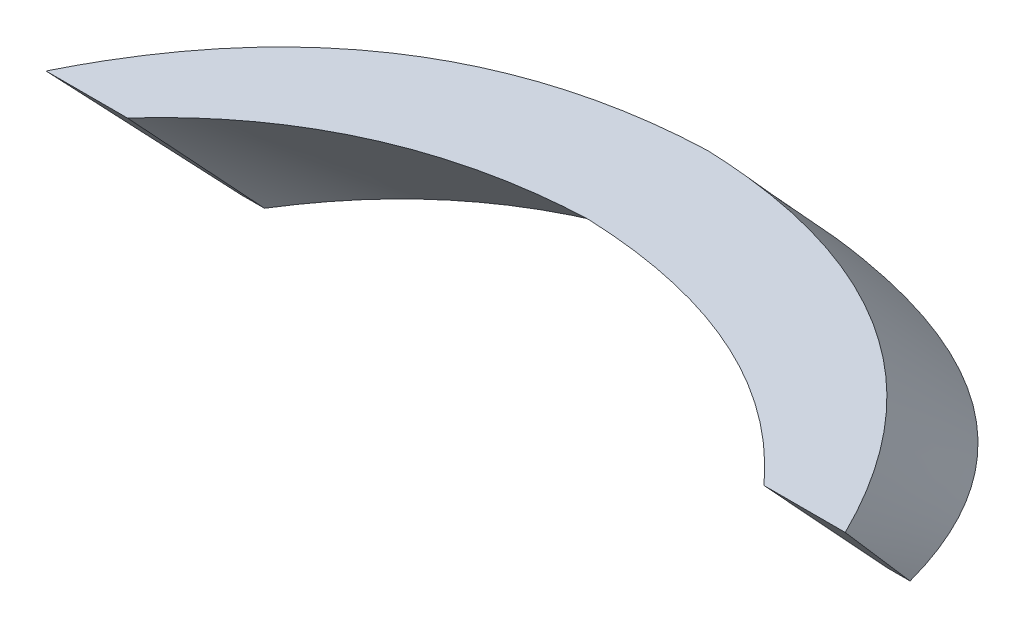
SolidWorks part; units mm, degrees
ref_plane "Front Plane" through (0, 0, 0) normal (0, 0, 1) x (1, 0, 0)
ref_plane "Top Plane" through (0, 0, 0) normal (0, 1, 0) x (1, 0, 0)
ref_plane "Right Plane" through (0, 0, 0) normal (1, 0, 0) x (0, 0, -1)
sketch "Sketch2" plane through (0, 0, 0) normal (0, 1, 0) x (1, 0, 0)
  line L0 (0, -5194.446) -> (0, 1731.482)
  line L1 (0, 0) -> (-18096.1342, 0) construction
  line L2 (0, 0) -> (-22098, -13277.818) construction
  line L3 (-22098, -15095.8741) -> (-22098, -12671.7993)
  line L4 (-22098, -12671.7993) -> (0, 1731.482)
  line L5 (-22098, -15095.8741) -> (0, -5194.446)
  line L6 (-9275.7037, -4314.3398) -> (-9275.7037, -5573.4051) construction
  line L7 (-9275.7037, -5573.4051) -> (-9275.7037, -9350.601) construction
  line L8 (-9275.7037, -5573.4051) -> (0, -5573.4051) construction
  line L9 (0, 346.2964) -> (-6827.52, -3825.6374)
  line L10 (0, -29565.6) -> (-7316.724, -34881.5112) construction
  line L11 (0, -29565.6) -> (-8167.6786, -29565.6) construction
  line L12 (0, -28507.0982) -> (0, -32741.1055)
  line L13 (-7316.724, -35992.9378) -> (-7316.724, -34511.0356)
  line L14 (-7316.724, -34511.0356) -> (0, -28507.0982)
  line L15 (0, -32741.1055) -> (-7316.724, -35992.9378)
  line L16 (-2399.2704, -30475.8849) -> (-2399.2704, -31308.772) construction
  line L17 (-2399.2704, -31308.772) -> (-2399.2704, -33807.4331) construction
  line L18 (-2399.2704, -31308.772) -> (0, -31308.772) construction
  line L19 (-6827.52, -3825.6374) -> (-6827.52, -6593.1427)
  line L20 (-6827.52, -6593.1427) -> (0, -3116.6676)
  line L21 (0, 346.2964) -> (0, -3116.6676) construction
  line L22 (0, -3116.6676) -> (0, 346.2964) construction
  line L23 (0, 346.2964) -> (0, -1385.1856) construction
  line L24 (0, 346.2964) -> (0, -3116.6676) construction
  line L25 (0, -1385.1856) -> (-6827.52, -5209.39) construction
  line L26 (0, 346.2964) -> (-22098, -13156.6142) construction
  line L27 (-3160.776, -1585.0854) -> (-3160.776, -3155.5874) construction
  line L28 (-3160.776, -3155.5874) -> (-3160.776, -4726.0893) construction
  line L29 (-3160.776, -3155.5874) -> (0, -3155.5874) construction
  dimension "Wing Sweep" = 31
  dimension "Half Span" = 22098
  dimension "Wing Root" = 6925.928
  dimension "D4" = 1731.482
  dimension "Wing Tip" = 2424.0748
  dimension "D6" = 606.0187
  dimension "Wing YBar" = 9275.7037
  dimension "Tail Sweep" = 36
  dimension "Tail Root" = 4234.0073
  dimension "D10" = 1058.5018
  dimension "Tail Tip" = 1481.9022
  dimension "D12" = 370.4756
  dimension "D13" = 7316.724
  dimension "Tail Ybar" = 2399.2704
  dimension "First Spar" = 1385.1856
  dimension "Second Spar" = 4848.1496
  dimension "Fuel Tip" = 2767.5053
  dimension "Tip Spar" = 484.815
  dimension "Fuel Ybar" = 3160.776
  dimension "Fuel Tank Length" = 6827.52
  dimension "Tail Arm" = 29565.6
sketch "Sketch4" plane through (0, 0, 0) normal (0, 1, 0) x (1, 0, 0)
  line L0 (0, 18200.9949) -> (0, -34834.2051) construction
  line L1 (-2240.28, 18200.9949) -> (2240.28, 18200.9949) construction
  line L2 (-2240.28, 11480.1549) -> (-2240.28, -25873.0851)
  line L3 (-2240.28, -34834.2051) -> (2240.28, -34834.2051) construction
  line L4 (2240.28, 11480.1549) -> (2240.28, -25873.0851)
  line L5 (0, -5194.446) -> (0, 1731.482) construction
  line L6 (-9275.7037, -5573.4051) -> (0, -5573.4051) construction
  line L7 (-2399.2704, -31308.772) -> (0, -31308.772) construction
  line L8 (0, 0) -> (-22098, -13277.818) construction
  line L9 (-22098, -12671.7993) -> (0, 1731.482) construction
  line L10 (-8451.85, 1616.4392) -> (-6132.83, 1616.4392)
  line L11 (-8451.85, 1616.4392) -> (-8451.85, -3941.0808)
  line L12 (-8451.85, -3941.0808) -> (-6132.83, -3941.0808)
  line L13 (-6132.83, 1616.4392) -> (-6132.83, -3941.0808)
  line L14 (2240.28, 11480.1549) -> (-2240.28, 11480.1549)
  arc A0 (-2240.28, -25873.0851) -> (2240.28, -25873.0851) centre (0, -25873.0851) ccw construction
  spline S0 degree 2 poles (-2240.28, 11480.1549) (-2010.8321, 15064.3252) (0, 18200.9949) knots 0 0 0 1 1 1 construction
  spline S1 degree 2 poles (2240.28, 11480.1549) (2010.8321, 15064.3252) (0, 18200.9949) knots 0 0 0 1 1 1 construction
  spline S2 degree 3 poles (-2240.28, -25873.0851) (-2042.135, -27711.7659) (-2075.1921, -30173.7144) (-919.8513, -32825.3563) (0, -32741.1055) knots 0 0 0 0 0.711043 1 1 1 1 construction
  spline S3 degree 3 poles (2240.28, -25873.0851) (2042.135, -27711.7659) (2075.1921, -30173.7144) (919.8513, -32825.3563) (0, -32741.1055) knots 0 0 0 0 0.711043 1 1 1 1 construction
  spline S4 degree 2 poles (-2240.28, -25873.0851) (-1878.6262, -27707.4335) (0, -28507.0982) knots 0 0 0 1 1 1
  spline S5 degree 2 poles (2240.28, -25873.0851) (1878.6262, -27707.4335) (0, -28507.0982) knots 0 0 0 1 1 1
  point P6 (0, 11480.1549)
  point P7 (0, -25873.0851)
  point P8 (0, -5573.4051)
  point P15 (0, -28113.3651)
  point P28 (-7292.34, 1616.4392)
  point P29 (-7292.34, -3021.6008)
  point P35 (-7292.34, -4381.6799)
  point P44 (-7292.34, -606.5688)
  dimension "Fuse Length" = 53035.2
  dimension "Fuse Dia" = 4480.56
  dimension "D3" = 6720.84
  dimension "D4" = 8961.12
  dimension "D6" = 7292.34
  dimension "Engine Dia" = 2319.02
  dimension "Engine Length" = 5557.52
  dimension "D9" = 4638.04
  dimension "D10" = 2223.008
  dimension "D11" = 4966.8362
  dimension "D2" = 23774.4
extrude "Boss-Extrude1" add sketch "Sketch4" along normal blind 76.2 contours L14 L2 S4 S5 L4
sketch "Sketch6" plane through (0, 0, 0) normal (0, 0, 1) x (1, 0, 0)
  line L0 (2240.28, 609.6) -> (-2240.28, 609.6) construction
  line L4 (-2240.28, 76.2) -> (-2240.28, 0) construction
  line L5 (2240.28, 76.2) -> (2240.28, 0) construction
  circle A2 centre (0, 609.6) radius 2240.28
  circle A3 centre (0, 609.6) radius 2151.38
  dimension "D2" = 88.9
  dimension "D1" = 4480.56
  dimension "D3" = 609.6
extrude "Boss-Extrude2" add sketch "Sketch6" along normal up to vertex (25873.0851 mm away) and the other way up to vertex (11480.1549 mm away) up to point (0, 0, 25873.0851) other way up to point (0, 0, -11480.1549)
sketch "Sketch38" plane through (0, 0, -11480.1549) normal (0, 0, -1) x (-1, 0, 0)
  arc A0 (-2155.7463, 0) -> (2155.7463, 0) centre (0, 609.6) ccw construction
  point P0 (0, -1630.68)
ref_plane "Plane1" through (0, 609.6, 0) normal (0, 1, 0) x (1, 0, 0)
sketch "Sketch9" plane through (0, 0, -11480.1549) normal (0, 0, -1) x (-1, 0, 0)
  circle A0 centre (0, 609.6) radius 2240.28
  arc A1 (2084.2074, 76.2) -> (-2084.2074, 76.2) centre (0, 609.6) ccw construction
  arc A2 (2175.8536, 76.2) -> (-2175.8536, 76.2) centre (0, 609.6) ccw construction
  circle A3 centre (0, 609.6) radius 2603.8351
extrude "Cut-Extrude2" cut sketch "Sketch9" against normal through all both and the other way through all
sketch "Sketch10" plane through (0, 0, 0) normal (0, 1, 0) x (1, 0, 0)
  line L0 (-22098, -12671.7993) -> (-2240.28, 271.2873)
  line L1 (-2240.28, 11480.1549) -> (-2240.28, -25873.0851) construction
  line L2 (-22098, -12671.7993) -> (-22098, -15095.8741)
  line L3 (-22098, -15095.8741) -> (-7292.34, -8461.9172)
  line L4 (-7292.34, -8461.9172) -> (-2240.28, -8461.9172)
  line L5 (-22098, -15095.8741) -> (0, -5194.446) construction
  line L6 (-22098, -12671.7993) -> (0, 1731.482) construction
  line L7 (-2240.28, -8461.9172) -> (-2240.28, 271.2873) construction
  line L8 (-2240.28, 271.2873) -> (-716.28, 271.2873)
  line L9 (-716.28, 271.2873) -> (-716.28, -8461.9172)
  line L10 (-716.28, -8461.9172) -> (-2240.28, -8461.9172)
  dimension "D1" = 1524
extrude "Boss-Extrude3" [suppressed] add sketch "Sketch10" along normal mid plane 6096
sketch "Sketch11" plane through (0, 0, 0) normal (0, 0, 1) x (1, 0, 0)
  line L0 (-2240.28, 304.8) -> (-22098, 2391.9305)
  line L2 (-22098, 2178.5705) -> (-2240.28, -304.8)
  line L3 (-2240.28, -304.8) -> (-2240.28, 304.8) construction
  line L4 (-22098, 2391.9305) -> (-17319.4154, 2391.9305) construction
  line L6 (-2240.28, 304.8) -> (-2240.28, 6258.5504)
  line L7 (-2240.28, 6258.5504) -> (-22098, 6258.5504)
  line L9 (-22098, -3521.01) -> (-2240.28, -3521.01)
  line L11 (-22098, 2391.9305) -> (-22098, 6258.5504)
  line L12 (-2240.28, -3521.01) -> (-2240.28, -304.8)
  line L13 (-22098, -3521.01) -> (-22098, 2178.5705)
  point P10 (-2240.28, 0)
  dimension "D1" = 6
  dimension "D2" = 19857.72
  dimension "D3" = 609.6
  dimension "D4" = 213.36
extrude "Cut-Extrude4" [suppressed] cut sketch "Sketch11" against normal through all both and the other way through all
sketch "Sketch12" [suppressed] plane through (0, 0, 0) normal (0, 0, 1) x (1, 0, 0)
  line L0 (-5140.2583, 609.6) -> (-2219.1422, 302.5783)
  line L1 (-5110.1542, 54.1013) -> (-2033.4072, -330.6711)
  line L2 (-2240.28, -304.8) -> (-22098, 2178.5705) construction
  line L3 (-22098, 2391.9305) -> (-2240.28, 304.8) construction
  arc A0 (-5110.1542, 54.1013) -> (-5140.2583, 609.6) centre (0, 609.6) ccw
  arc A1 (2084.2074, 76.2) -> (-2084.2074, 76.2) centre (0, 609.6) ccw construction
  arc A2 (-2033.4072, -330.6711) -> (-2219.1422, 302.5783) centre (0, 609.6) ccw
  circle A3 centre (0, 609.6) radius 2240.28 construction
extrude "Cut-Extrude5" [suppressed] cut sketch "Sketch12" against normal through all both and the other way through all
sketch "Sketch13" [suppressed] plane through (0, 0, 0) normal (0, 0, 1) x (1, 0, 0)
  line L0 (-716.28, 2638.2397) -> (-716.28, 76.2)
  line L1 (-716.28, 76.2) -> (-2084.2074, 76.2)
  line L2 (-716.28, -1419.0397) -> (-716.28, 0)
  line L3 (-716.28, 0) -> (-2063.2072, 0)
  line L4 (2240.28, 0) -> (-2240.28, 0) construction
  line L5 (2084.2074, 76.2) -> (-2084.2074, 76.2) construction
  line L7 (-716.28, 2638.2397) -> (-716.28, 76.2) construction
  arc A0 (-716.28, 2638.2397) -> (-2084.2074, 76.2) centre (0, 609.6) ccw
  arc A1 (2084.2074, 76.2) -> (-2084.2074, 76.2) centre (0, 609.6) ccw construction
  arc A2 (-2063.2072, 0) -> (-716.28, -1419.0397) centre (0, 609.6) ccw
extrude "Cut-Extrude6" [suppressed] cut sketch "Sketch13" against normal up to next and the other way up to next
sketch "Sketch14" plane through (0, 0, 0) normal (1, 0, 0) x (0, 0, -1)
  line L0 (-28507.0982, 0) -> (-32741.1055, 0) construction
  line L1 (18200.9949, 0) -> (-34834.2051, 0) construction
  spline S0 degree 2 poles (-25873.0851, -1630.68) (-29480.6383, -1395.4674) (-32741.1055, 0) knots 0 0 0 1 1 1
  spline S1 degree 2 poles (-25873.0851, 2849.88) (-38574.5003, 2679.8095) (-32741.1055, 0) knots 0 0 0 1 1 1
  point P2 (-32741.1055, 2379.2416)
  point P25 (-34573.6218, 1489.0046)
ref_plane "Plane2" through (0, 0, 31657.7766) normal (0, 0, 1) x (1, 0, 0)
ref_plane "Plane4" through (0, 0, 34113.407) normal (0, 0, 1) x (1, 0, 0)
ref_plane "Plane5" through (0, 0, 34418.207) normal (0, 0, 1) x (1, 0, 0)
sketch "Sketch15" plane through (0, 0, 31657.7766) normal (0, 0, 1) x (1, 0, 0)
  spline S0 degree 3 poles (-2286.8585, -200.6896) (0, 4376.1132) (2286.8585, -200.6896) (0, -503.66) (-2286.8585, -200.6896) (0, 4376.1132) (2286.8585, -200.6896) knots -0.665946 -0.5 -0.334054 0 0.334054 0.5 0.665946 1 1.334054 1.5 1.665946 only from (0, 2543.0199) to (0, 2543.0199)
sketch "Sketch16" plane through (0, 0, 25873.0851) normal (0, 0, 1) x (1, 0, 0)
  circle A0 centre (0, 609.6) radius 2240.28
  arc A1 (2175.8536, 76.2) -> (-2175.8536, 76.2) centre (0, 609.6) ccw construction
sketch "Sketch17" plane through (0, 0, 34418.207) normal (0, 0, 1) x (1, 0, 0)
  circle A0 centre (0, 1489.0046) radius 355.2599
  point P0 (0, 1489.0046)
loft "Loft1" add profiles "Sketch16", "Sketch15", "Sketch17" start constraint default end constraint default connector at (-1975.9164, 1665.3503, 25873.0851) connector at (-1045.2699, 1802.0343, 31657.7766) connector at (-328.3879, 1624.5441, 34418.2069)
sketch "Sketch18" plane through (0, 0, 0) normal (1, 0, 0) x (0, 0, -1)
  line L0 (-34573.6218, 1489.0046) -> (-34418.207, 1489.0046) construction
  line L1 (-34418.207, 1844.2644) -> (-34418.207, 1133.7447) construction
  line L4 (-34418.207, 1844.2644) -> (-34418.207, 1489.0046)
  line L5 (-34418.207, 1489.0046) -> (-34573.6218, 1489.0046)
  arc A0 (-34418.207, 1844.2644) -> (-34573.6218, 1489.0046) centre (-34050.8281, 1471.9234) ccw
revolve "Revolve2" [suppressed] add sketch "Sketch18" angle 360 about L0
sketch "Sketch19" plane through (0, 0, 0) normal (1, 0, 0) x (0, 0, -1)
  line L1 (15310.2867, 1766.9705) -> (20771.0558, -220.5869) construction
  line L2 (15310.2867, 1766.9705) -> (21563.626, 1766.9705) construction
  line L3 (12222.5489, -1630.68) -> (11480.1549, -1630.68)
  line L4 (14485.9128, -1630.68) -> (12344.0382, -1630.68) construction
  spline S0 degree 3 poles (11480.1549, 2849.88) (12129.2973, 2828.9264) (13715.2662, 2683.4296) (15217.8604, 2079.5383) (15795.8225, 1202.5082) knots 0 0 0 0 0.4097 1 1 1 1
  spline S1 degree 3 poles (12222.5489, -1630.68) (13561.2205, -1630.68) (16529.3441, -1728.2677) (19075.8101, 527.5528) (16077.7145, 711.2856) (15795.8225, 1202.5082) knots 0.196369 0.196369 0.196369 0.196369 0.613709 0.726581 1 1 1 1
  point P0 (11480.1549, 2849.88)
  dimension "D1" = 20
ref_plane "Plane6" through (0, 0, -12639.1444) normal (0, 0, -1) x (-1, 0, 0)
ref_plane "Plane7" through (0, 0, -13414.8443) normal (0, 0, -1) x (-1, 0, 0)
ref_plane "Plane8" through (0, 0, -13986.0105) normal (0, 0, -1) x (-1, 0, 0)
ref_plane "Plane9" through (0, 0, -15310.2867) normal (0, 0, -1) x (-1, 0, 0)
ref_plane "Plane10" through (0, 0, -15795.8225) normal (0, 0, -1) x (-1, 0, 0)
ref_plane "Plane11" through (0, 0, -16773.3437) normal (0, 0, -1) x (-1, 0, 0)
ref_plane "Plane12" through (0, 0, -17435.7391) normal (0, 0, -1) x (-1, 0, 0)
ref_plane "Plane13" through (0, 0, -17740.5391) normal (0, 0, -1) x (-1, 0, 0)
sketch "Sketch39" plane through (0, 0, -11480.1549) normal (0, 0, -1) x (-1, 0, 0)
  circle A0 centre (0, 609.6) radius 2240.28
  circle A1 centre (0, 609.6) radius 2240.28 construction
sketch "Sketch20" plane through (0, 0, -17435.7391) normal (0, 0, -1) x (-1, 0, 0)
  spline S0 degree 3 poles (-701.9217, -44.4557) (0, 782.804) (701.9217, -44.4557) (0, -1231.5737) (-701.9217, -44.4557) (0, 782.804) (701.9217, -44.4557) knots -0.783794 -0.5 -0.216206 0 0.216206 0.5 0.783794 1 1.216206 1.5 1.783794 only from (0, 533.0732) to (0, 533.0732)
sketch "Sketch22" plane through (0, 0, -16773.3437) normal (0, 0, -1) x (-1, 0, 0)
  spline S0 degree 3 poles (-1232.0931, -20.3589) (0, 1063.9091) (1232.0931, -20.3589) (0, -1730.0791) (-1232.0931, -20.3589) (0, 1063.9091) (1232.0931, -20.3589) knots -0.779149 -0.5 -0.220851 0 0.220851 0.5 0.779149 1 1.220851 1.5 1.779149 only from (0, 731.7157) to (0, 731.7157)
sketch "Sketch23" plane through (0, 0, -15795.8225) normal (0, 0, -1) x (-1, 0, 0)
  spline S0 degree 3 poles (-1882.733, -3.3648) (0, 1781.8268) (1882.733, -3.3648) (0, -2124.6415) (-1882.733, -3.3648) (0, 1781.8268) (1882.733, -3.3648) knots -0.759793 -0.5 -0.240207 0 0.240207 0.5 0.759793 1 1.240207 1.5 1.759793 only from (0, 1202.5082) to (0, 1202.5082)
sketch "Sketch24" plane through (0, 0, -15310.2867) normal (0, 0, -1) x (-1, 0, 0)
  spline S0 degree 3 poles (-2165.5189, 16.3716) (0, 2684.4722) (2165.5189, 16.3716) (0, -2201.7865) (-2165.5189, 16.3716) (0, 2684.4722) (2165.5189, 16.3716) knots -0.737946 -0.5 -0.262054 0 0.262054 0.5 0.737946 1 1.262054 1.5 1.737946 only from (0, 1766.9705) to (0, 1766.9705)
sketch "Sketch25" plane through (0, 0, -13986.0105) normal (0, 0, -1) x (-1, 0, 0)
  spline S0 degree 3 poles (-2806.4363, 33.6044) (0, 3851.8744) (2806.4363, 33.6044) (0, -2337.0146) (-2806.4363, 33.6044) (0, 3851.8744) (2806.4363, 33.6044) knots -0.720945 -0.5 -0.279055 0 0.279055 0.5 0.720945 1 1.279055 1.5 1.720945 only from (0, 2484.1811) to (0, 2484.1811)
sketch "Sketch26" plane through (0, 0, -13414.8443) normal (0, 0, -1) x (-1, 0, 0)
  spline S0 degree 3 poles (-3011.6576, 21.7792) (0, 4101.142) (3011.6576, 21.7792) (0, -2350.0256) (-3011.6576, 21.7792) (0, 4101.142) (3011.6576, 21.7792) knots -0.718807 -0.5 -0.281193 0 0.281193 0.5 0.718807 1 1.281193 1.5 1.718807 only from (0, 2632.7632) to (0, 2632.7632)
sketch "Sketch27" [suppressed] plane through (0, 0, -12639.1444) normal (0, 0, -1) x (-1, 0, 0)
  spline S0 degree 3 poles (-3226.2661, 1.2518) (0, 4325.3039) (3226.2661, 1.2518) (0, -2339.458) (-3226.2661, 1.2518) (0, 4325.3039) (3226.2661, 1.2518) knots -0.717159 -0.5 -0.282841 0 0.282841 0.5 0.717159 1 1.282841 1.5 1.717159 only from (0, 2763.0215) to (0, 2763.0215)
sketch "Sketch36" plane through (0, 0, -17740.5391) normal (0, 0, -1) x (-1, 0, 0)
  circle A0 centre (0, 0) radius 286.4473
extrude "Boss-Extrude5" add sketch "Sketch39" along normal up to surface (1158.9894 mm away) up to plane "Plane6"
ref_point "Point1" parameters "D1"=1219.2
ref_plane "Plane14" through (0, 2052.6296, 0) normal (0, 1, 0) x (1, 0, 0)
sketch "Sketch41" plane through (0, 2052.6296, 0) normal (0, 1, 0) x (1, 0, 0)
  line L0 (0, 13024.042) -> (0, 19562.306) construction
  line L1 (-1729.621, 13800.6829) -> (-1377.1429, 13800.6829)
  line L2 (1729.621, 13800.6829) -> (1377.1429, 13800.6829)
  spline S0 degree 2 poles (-1729.621, 13800.6829) (-1193.6069, 14891.1922) (0, 14934.4558) knots 0 0 0 1 1 1
  spline S1 degree 2 poles (-1377.1429, 13800.6829) (-850.6483, 14385.3251) (0, 14418.3833) knots 0 0 0 1 1 1
  spline S2 degree 2 poles (1729.621, 13800.6829) (1193.6069, 14891.1922) (0, 14934.4558) knots 0 0 0 1 1 1
  spline S3 degree 2 poles (1377.1429, 13800.6829) (850.6483, 14385.3251) (0, 14418.3833) knots 0 0 0 1 1 1
  point P10 (972.0057, 14665.3)
  point P12 (0, 0)
ref_point "Point2" parameters "D1"=304.8
ref_plane "Plane15" through (0, 1447.9922, 0) normal (0, 1, 0) x (1, 0, 0)
sketch "Sketch42" plane through (0, 1447.9922, 0) normal (0, 1, 0) x (1, 0, 0)
  line L0 (0, 18200.9949) -> (0, -34834.2051) construction
  line L1 (-1447.3744, 14363.483) -> (-1346.8474, 14363.483)
  line L2 (0, -2479.4252) -> (0, 2479.4252) construction
  line L3 (1447.3744, 14363.483) -> (1346.8474, 14363.483)
  line L4 (0, 15180.0889) -> (0, 15488.7066) construction
  spline S0 degree 2 poles (-1447.3744, 14363.483) (-1182.13, 15348.8535) (0, 15488.7066) knots 0 0 0 1 1 1
  spline S1 degree 2 poles (-1346.8474, 14363.483) (-892.2541, 15093.5273) (0, 15180.0889) knots 0 0 0 1 1 1
  spline S2 degree 2 poles (1447.3744, 14363.483) (1182.13, 15348.8535) (0, 15488.7066) knots 0 0 0 1 1 1
  spline S3 degree 2 poles (1346.8474, 14363.483) (892.2541, 15093.5273) (0, 15180.0889) knots 0 0 0 1 1 1
  point P1 (-1447.3744, 14363.483)
  point P5 (0, 15539.043)
  point P13 (-1248.9801, 14816.412)
  point P15 (0, 15509.9346)
  point P18 (0, 15488.7066)
loft "Loft2" add profiles "Sketch41", "Sketch42" connector at (0, 2052.6296, -14934.4558) connector at (0, 1447.9922, -15488.7066)
sketch "Sketch40" plane through (0, 0, -12639.1444) normal (0, 0, -1) x (-1, 0, 0)
  line L1 (-11123.8565, -9219.5535) -> (11123.8565, -9219.5535)
  line L2 (-11123.8565, -9219.5535) -> (-11123.8565, 9219.5535)
  line L3 (-11123.8565, 9219.5535) -> (11123.8565, 9219.5535)
  line L4 (11123.8565, -9219.5535) -> (11123.8565, 9219.5535)
  line L5 (-11123.8565, -9219.5535) -> (11123.8565, 9219.5535) construction
  line L6 (-11123.8565, 9219.5535) -> (11123.8565, -9219.5535) construction
  point P0 (0, 0)
extrude "Cut-Extrude9" cut sketch "Sketch40" against normal through all
equation "\"D6@Sketch2\" = \"Wing Tip@Sketch2\" / 4"
equation "\"D4@Sketch2\" = \"Wing Root@Sketch2\" / 4"
equation "\"D10@Sketch2\" = \"Tail Root@Sketch2\" / 4"
equation "\"D12@Sketch2\" = \"Tail Tip@Sketch2\" / 4"
equation "\"D13@Sketch2\"=48.01/2"
equation "\"First Spar@Sketch2\"=0.2 * \"Wing Root@Sketch2\""
equation "\"Second Spar@Sketch2\"   = 0.7 * \"Wing Root@Sketch2\""
equation "\"Tip Spar@Sketch2\"=0.2 * \"Wing Tip@Sketch2\""
equation "\"D3@Sketch4\" = 1.5 * \"Fuse Dia@Sketch4\""
equation "\"D4@Sketch4\" = 2 * \"Fuse Dia@Sketch4\""
equation "\"D6@Sketch4\" = 0.33 * \"Half Span@Sketch2\""
equation "\"D9@Sketch4\" = 2 * \"Engine Dia@Sketch4\""
equation "\"D10@Sketch4\" = 0.40 * \"Engine Length@Sketch4\""
equation "\"D4@Sketch11\"=.35*\"D3@Sketch11\""
